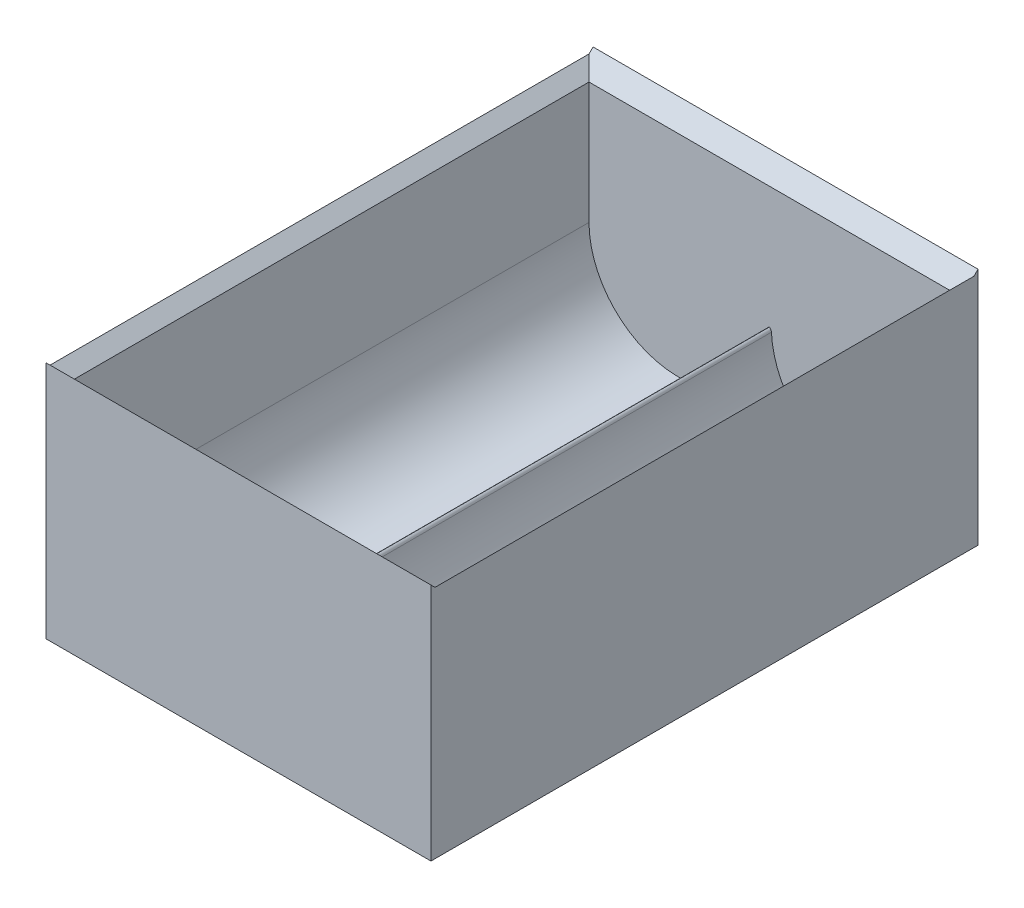
SolidWorks part; units mm, degrees
ref_plane "Front Plane" through (0, 0, 0) normal (0, 0, 1) x (1, 0, 0)
ref_plane "Top Plane" through (0, 0, 0) normal (0, 1, 0) x (1, 0, 0)
ref_plane "Right Plane" through (0, 0, 0) normal (1, 0, 0) x (0, 0, -1)
sketch "Sketch1" plane through (0, 0, 0) normal (0, 1, 0) x (1, 0, 0)
  line L1 (-47.5, 67.5) -> (47.5, 67.5)
  line L2 (-47.5, 67.5) -> (-47.5, -67.5)
  line L3 (-47.5, -67.5) -> (47.5, -67.5)
  line L4 (47.5, 67.5) -> (47.5, -67.5)
  line L5 (-47.5, 67.5) -> (47.5, -67.5) construction
  line L6 (-47.5, -67.5) -> (47.5, 67.5) construction
  point P0 (0, 0)
  dimension "D1" = 135
  dimension "D2" = 95
extrude "Boss-Extrude1" add sketch "Sketch1" along normal blind 65
ref_plane "Plane1" through (0, 0, 63.5) normal (0, 0, 1) x (1, 0, 0)
sketch "Sketch2" plane through (0, 0, 63.5) normal (0, 0, 1) x (1, 0, 0)
  line L0 (-47.5, 65) -> (-47.5, 0) construction
  line L1 (0, 0) -> (0, 33.8796) construction
  line L7 (-44.5, 25) -> (-44.5, 70)
  line L8 (-44.5, 70) -> (44.5, 70)
  line L9 (44.5, 25) -> (44.5, 70)
  line L11 (-0.5, 25) -> (0.5, 25)
  line L12 (-47.5, 0) -> (47.5, 0) construction
  arc A4 (-44.5, 25) -> (-0.5, 25) centre (-22.5, 25) ccw
  arc A5 (44.5, 25) -> (0.5, 25) centre (22.5, 25) cw
  point P8 (-0.8345, 21.2878)
  point P13 (0, 70)
  point P14 (0, 0)
  point P15 (-22.6302, 22.8628)
  point P16 (23.5522, 22.0369)
  point P18 (0, 0)
  point P19 (0, 0)
  dimension "D1" = 22
  dimension "D2" = 22
  dimension "D3" = 3
  dimension "D4" = 45
  dimension "D5" = 25
extrude "Cut-Extrude1" cut sketch "Sketch2" against normal offset from surface (127 mm away) 4 contours L9 L8 L7 region at (0, 38.739, 63.5) up to face at (0, 32.5, -67.5)
fillet "Fillet1" radius 1 2 edges at (0.5, 25, 0) (-0.5, 25, 0)
chamfer "Chamfer1" distance 10 angle 45 4 edges at (0, 65, 63.5) (44.5, 65, 0) (-44.5, 65, 0) (0, 65, -63.5)
